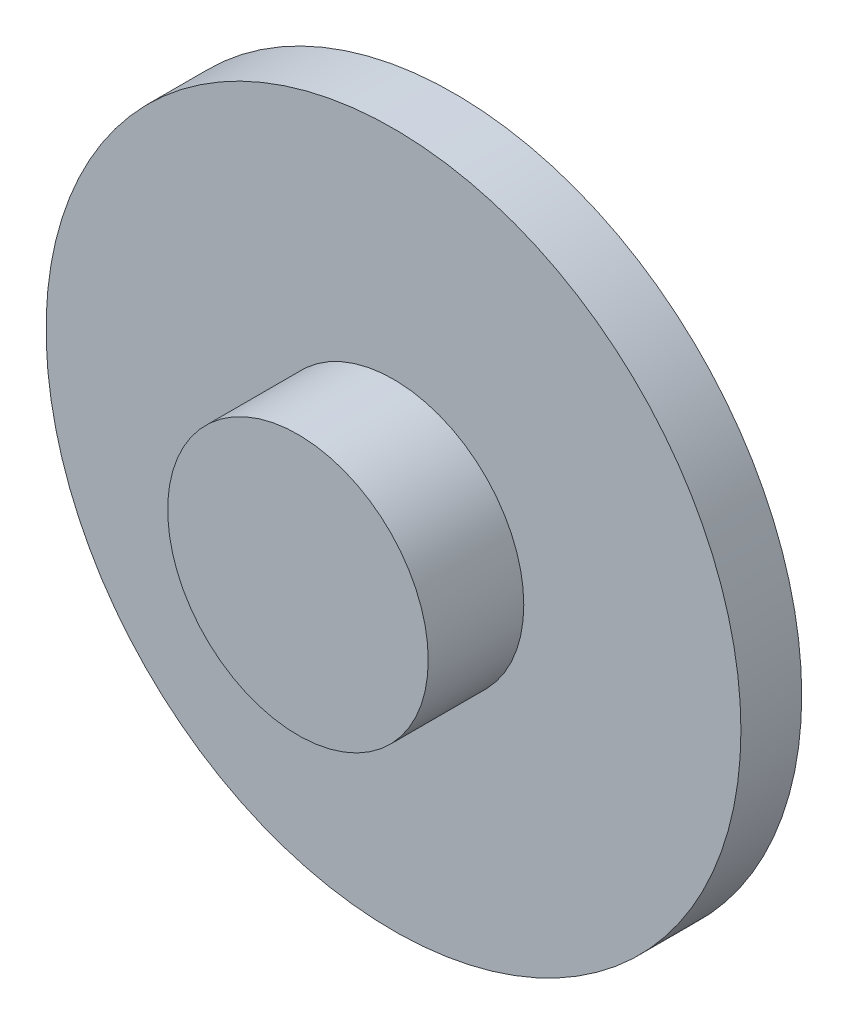
SolidWorks part; units mm, degrees
ref_plane "Front Plane" through (0, 0, 0) normal (0, 0, 1) x (1, 0, 0)
ref_plane "Top Plane" through (0, 0, 0) normal (0, 1, 0) x (1, 0, 0)
ref_plane "Right Plane" through (0, 0, 0) normal (1, 0, 0) x (0, 0, -1)
sketch "Sketch2" plane through (0, 0, 0) normal (0, 0, 1) x (1, 0, 0)
  circle A0 centre (0, 0) radius 10.16
  circle A2 centre (0, 0) radius 3.81
  dimension "D1" = 20.32
  dimension "D5" = 7.62
extrude "Boss-Extrude1" add sketch "Sketch2" along normal blind 1.778 contours A0 A2 region at (-9.8726, 0, 0)
extrude "Boss-Extrude2" add sketch "Sketch2<3>" along normal blind 1.778
sketch "Sketch2<3>" plane through (0, 0, 0) normal (0, 0, 1) x (1, 0, 0) same geometry as "Sketch2"
extrude "Boss-Extrude3" add sketch "Sketch2<4>" along normal blind 4.572 contours A2 region at (0, 0, 0)
sketch "Sketch2<4>" plane through (0, 0, 0) normal (0, 0, 1) x (1, 0, 0) same geometry as "Sketch2"
